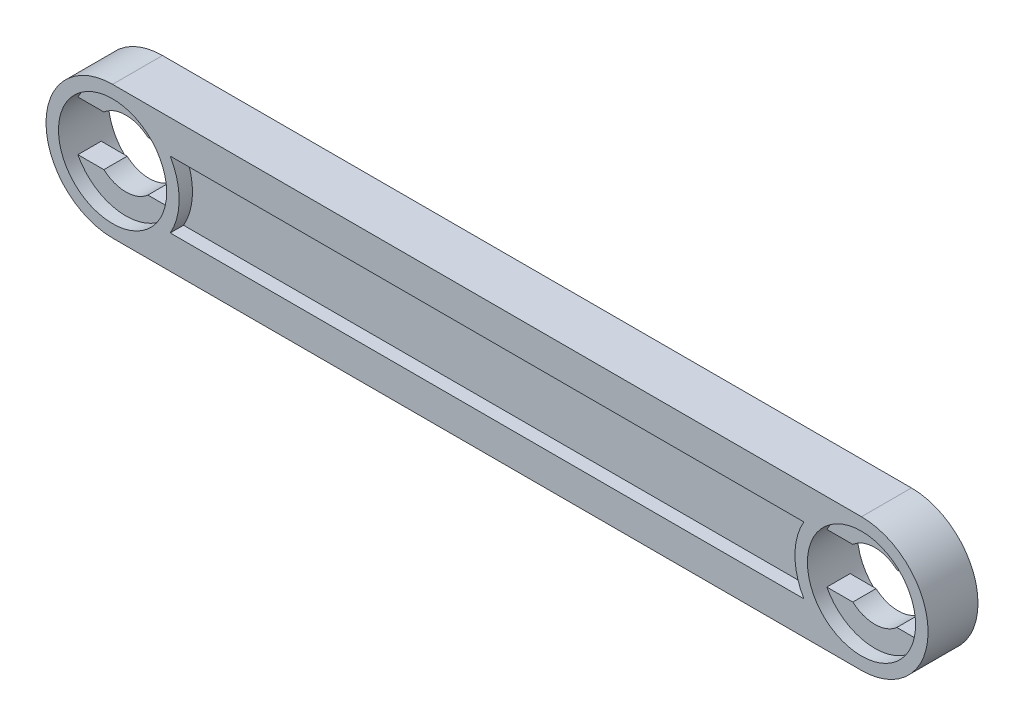
SolidWorks part; units mm, degrees
ref_plane "前视基准面" through (0, 0, 0) normal (0, 0, 1) x (1, 0, 0)
ref_plane "上视基准面" through (0, 0, 0) normal (0, 1, 0) x (1, 0, 0)
ref_plane "右视基准面" through (0, 0, 0) normal (1, 0, 0) x (0, 0, -1)
sketch "草图1" plane through (0, 0, 0) normal (0, 0, 1) x (1, 0, 0)
  line L1 (0, 4) -> (45, 4)
  line L3 (0, -4) -> (45, -4)
  arc A0 (0, 4) -> (0, -4) centre (0, 0) ccw
  arc A1 (45, -4) -> (45, 4) centre (45, 0) ccw
extrude "凸台-拉伸1" add sketch "草图1" against normal blind 3
sketch "草图2" plane through (0, 0, 0) normal (0, 0, 1) x (1, 0, 0)
  line L0 (1.3229, -1.5) -> (2.8831, -1.5)
  line L1 (-2.8831, -1.5) -> (-1.3229, -1.5)
  line L2 (1.3229, 1.5) -> (2.8831, 1.5)
  line L3 (-2.8831, 1.5) -> (-1.3229, 1.5)
  arc A0 (1.3229, 1.5) -> (-1.3229, 1.5) centre (0, 0) ccw
  arc A1 (-2.8831, 1.5) -> (-2.8831, -1.5) centre (0, 0) ccw
  arc A3 (2.8831, -1.5) -> (2.8831, 1.5) centre (0, 0) ccw
  arc A4 (-1.3229, -1.5) -> (1.3229, -1.5) centre (0, 0) ccw
extrude "切除-拉伸1" cut sketch "草图2" against normal up to next
sketch "草图3" plane through (0, 0, 0) normal (0, 0, 1) x (1, 0, 0)
  circle A1 centre (0, 0) radius 3.25
extrude "切除-拉伸2" cut sketch "草图3" against normal blind 0.8
extrude "切除-拉伸3" cut sketch "草图3<2>" along normal blind 0.8 from offset 3 offset against normal yes
sketch "草图3<2>" plane through (0, 0, 0) normal (0, 0, 1) x (1, 0, 0) same geometry as "草图3"
ref_plane "基准面1" through (22.5, 0, 0) normal (1, 0, 0) x (0, 0, -1)
mirror "镜向1" about plane through (22.5, 0, 0) normal (1, 0, 0) of "切除-拉伸3", "切除-拉伸2", "切除-拉伸1"
sketch "草图4" plane through (0, 0, 0) normal (0, 0, 1) x (1, 0, 0)
  line L0 (3.4641, 2) -> (41.5359, 2)
  line L2 (3.4641, -2) -> (41.5359, -2)
  arc A0 (3.4641, -2) -> (3.4641, 2) centre (0, 0) ccw
  arc A1 (41.5359, 2) -> (41.5359, -2) centre (45, 0) ccw
extrude "切除-拉伸4" cut sketch "草图4" against normal blind 0.8
sketch "草图5" plane through (0, 0, -3) normal (0, 0, -1) x (-1, 0, 0)
  line L1 (-41, -2) -> (-4, -2)
  line L2 (-41, -2) -> (-41, 2)
  line L3 (-41, 2) -> (-4, 2)
  line L4 (-4, -2) -> (-4, 2)
extrude "切除-拉伸5" cut sketch "草图5" against normal blind 0.8
